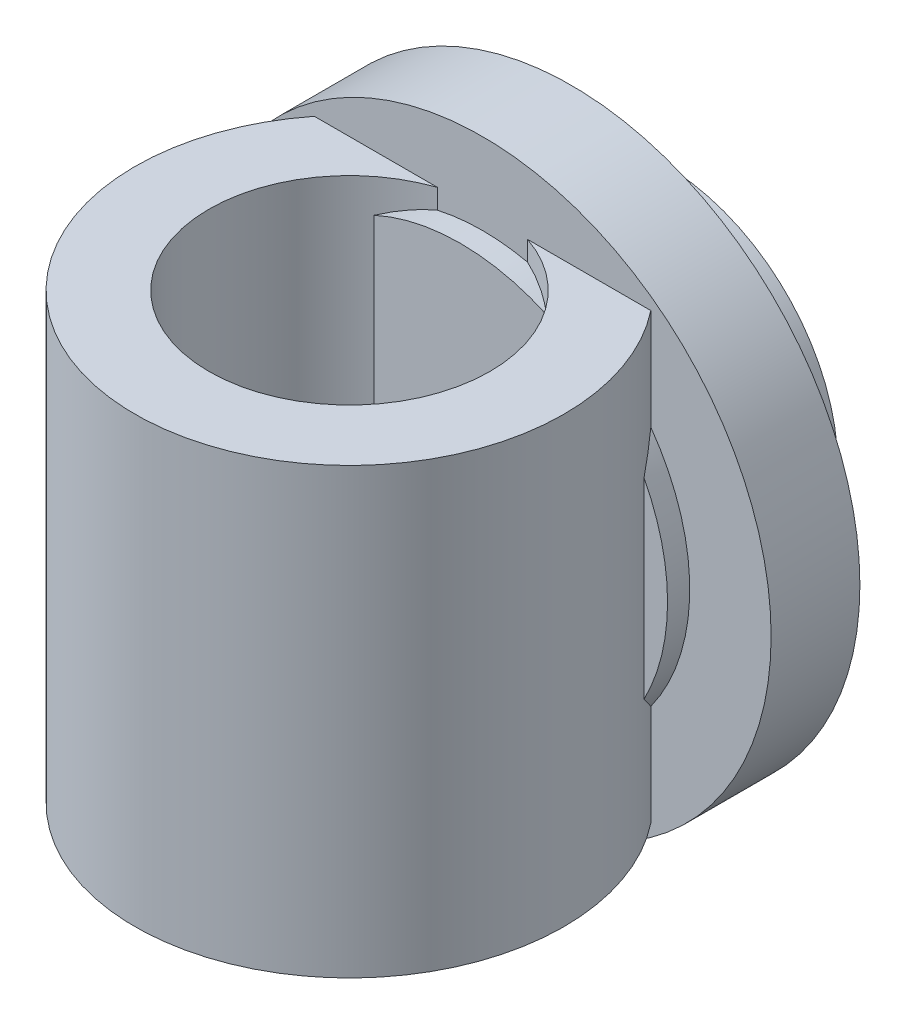
SolidWorks part; units mm, degrees
ref_plane "前视基准面" through (0, 0, 0) normal (0, 0, 1) x (1, 0, 0)
ref_plane "上视基准面" through (0, 0, 0) normal (0, 1, 0) x (1, 0, 0)
ref_plane "右视基准面" through (0, 0, 0) normal (1, 0, 0) x (0, 0, -1)
other "Configuration Table"
sketch "草图1" plane through (0, 0, 0) normal (0, 0, 1) x (1, 0, 0)
  circle A0 centre (0, 0) radius 47
extrude "凸台-拉伸1" add sketch "草图1" against normal blind 25
sketch "草图2" plane through (0, 0, 0) normal (0, 0, 1) x (1, 0, 0)
  circle A0 centre (0, 0) radius 78
extrude "凸台-拉伸2" add sketch "草图2" along normal blind 24
sketch "草图3" plane through (0, 0, 0) normal (0, 0, 1) x (1, 0, 0)
  circle A0 centre (0, 0) radius 56
extrude "凸台-拉伸3" add sketch "草图3" along normal blind 30
sketch "草图4" plane through (0, 0, 0) normal (0, 1, 0) x (1, 0, 0)
  circle A0 centre (0, -60) radius 38
  circle A1 centre (0, -60) radius 58
extrude "凸台-拉伸4" add sketch "草图4" along normal blind 60 and the other way blind 60
